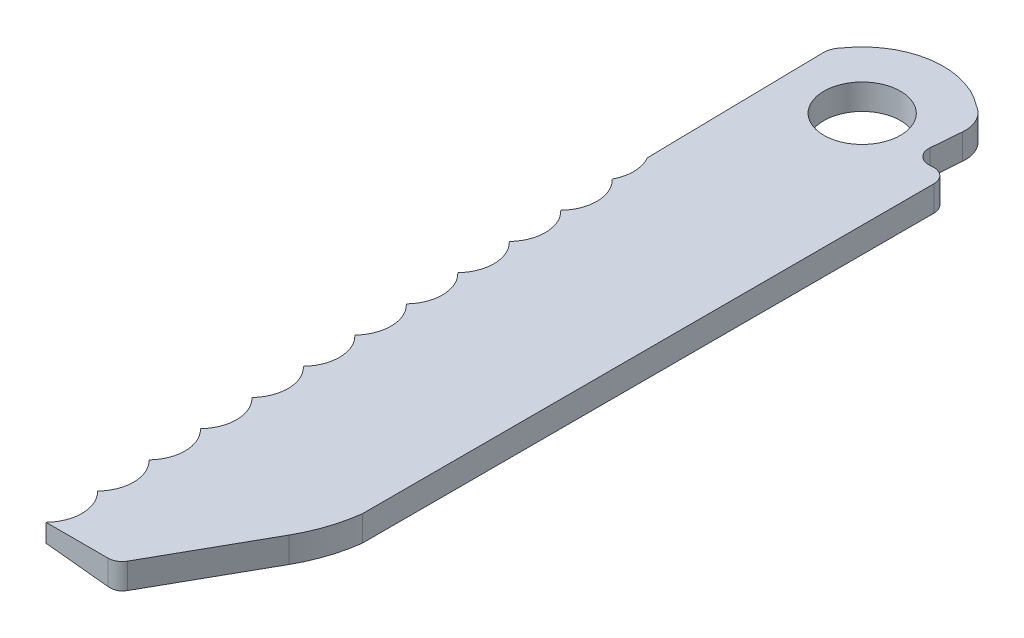
SolidWorks part; units mm, degrees
ref_plane "Front Plane" through (0, 0, 0) normal (0, 0, 1) x (1, 0, 0)
ref_plane "Top Plane" through (0, 0, 0) normal (0, 1, 0) x (1, 0, 0)
ref_plane "Right Plane" through (0, 0, 0) normal (1, 0, 0) x (0, 0, -1)
sketch "Sketch1" plane through (0, 0, 0) normal (0, 1, 0) x (1, 0, 0)
  line L0 (16.7853, 37.7669) -> (83.9265, 37.7669) construction
  line L1 (58.5595, 61.2582) -> (58.3532, 58.7408)
  line L2 (60.2335, 26.7373) -> (60.2335, 58.807)
  line L3 (58.3532, 58.7408) -> (60.2335, 58.807)
  line L4 (59.2323, 23.7058) -> (55.8327, 17.6675)
  line L5 (51.983, 17.6675) -> (55.8327, 17.6675)
  line L6 (50.9908, 61.1729) -> (51.1623, 51.4011)
  line L7 (51.1623, 51.4011) -> (51.983, 17.6675) construction
  arc A0 (51.2963, 61.9533) -> (57.6891, 62.876) centre (54.9292, 59.3902) cw
  arc A1 (51.2963, 61.9533) -> (50.9908, 61.1729) centre (52.0909, 61.1922) ccw
  arc A2 (57.6891, 62.876) -> (58.5595, 61.2582) centre (56.8772, 61.3961) cw
  arc A3 (60.2335, 26.7373) -> (59.2323, 23.7058) centre (52.0096, 27.7723) cw
  arc A4 (51.1623, 51.4011) -> (51.2102, 49.4312) centre (49.4031, 50.3728) cw
  arc A5 (51.9128, 20.5551) -> (51.983, 17.6675) centre (50.5108, 19.0764) cw
  arc A6 (51.9128, 20.5551) -> (51.8425, 23.4427) centre (50.4405, 21.964) ccw
  arc A7 (51.7722, 26.3303) -> (51.8425, 23.4427) centre (50.3703, 24.8516) cw
  arc A8 (51.7722, 26.3303) -> (51.702, 29.218) centre (50.3, 27.7392) ccw
  arc A9 (51.6317, 32.1056) -> (51.702, 29.218) centre (50.2298, 30.6268) cw
  arc A10 (51.6317, 32.1056) -> (51.5615, 34.9932) centre (50.1595, 33.5144) ccw
  arc A11 (51.4912, 37.8808) -> (51.5615, 34.9932) centre (50.0893, 36.402) cw
  arc A12 (51.421, 40.7684) -> (51.4912, 37.8808) centre (50.019, 39.2896) cw
  arc A13 (51.421, 40.7684) -> (51.3507, 43.656) centre (49.9488, 42.1772) ccw
  arc A14 (51.2102, 49.4312) -> (51.2805, 46.5436) centre (49.8082, 47.9525) cw
  arc A15 (51.2805, 46.5436) -> (51.3507, 43.656) centre (49.8785, 45.0648) cw
  circle A16 centre (54.9292, 59.3902) radius 2.0955
  point P10 (0, 0)
  point P43 (0, 0)
  point P44 (0, 0)
  point P45 (0, 0)
  point P46 (0, 0)
  point P47 (0, 0)
  point P48 (0, 0)
  point P49 (0, 0)
  point P50 (0, 0)
  point P51 (0, 0)
  point P52 (0, 0)
  point P53 (0, 0)
  point P54 (0, 0)
  point P55 (0, 0)
  point P56 (0, 0)
  point P57 (49.8367, 24.2764)
  point P58 (0, 0)
  dimension "D1" = 4.191
  dimension "D3" = 4.4461
  dimension "D7" = 6.9295
  dimension "D8" = 3.8497
  dimension "D9" = 32.0697
  dimension "D10" = 1.1003
  dimension "D11" = 1.6879
  dimension "D12" = 2.0377
  dimension "D2" = 1.005
  dimension "D4" = 1.8804
  dimension "D5" = 2.5258
  dimension "D6" = 43.5054
extrude "Boss-Extrude1" add sketch "Sketch1" along normal blind 1.397
sketch "Sketch2" plane through (0, 0, 0) normal (0, 0, 1) x (1, 0, 0)
  line L0 (55.8327, 0) -> (50.9908, 0.5089)
  line L1 (50.9908, 1.397) -> (50.9908, 0) construction
  line L2 (50.9908, 0.5089) -> (50.9908, 0)
  line L3 (50.9908, 0) -> (55.8327, 0)
  point P5 (60.2335, 0)
  point P8 (55.8327, 0)
  dimension "D1" = 6
extrude "Cut-Extrude1" cut sketch "Sketch2" against normal blind 52.451
fillet "Fillet1" radius 0.762 3 edges at (60.2335, 0.6985, -58.807) (58.3532, 0.6985, -58.7408) (55.8327, 0.6985, -17.6675)
